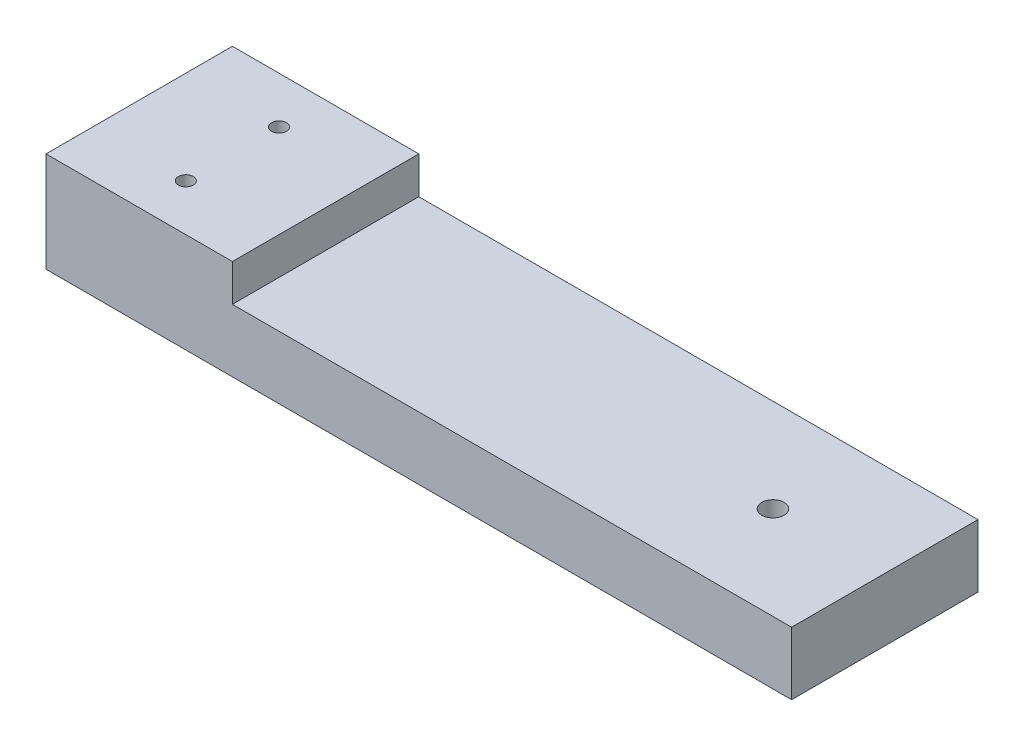
SolidWorks part; units mm, degrees
material "Balsa"
ref_plane "Front Plane" through (0, 0, 0) normal (0, 0, 1) x (1, 0, 0)
ref_plane "Top Plane" through (0, 0, 0) normal (0, 1, 0) x (1, 0, 0)
ref_plane "Right Plane" through (0, 0, 0) normal (1, 0, 0) x (0, 0, -1)
sketch "Sketch1" plane through (0, 0, 0) normal (0, 1, 0) x (1, 0, 0)
  line L1 (0, 0) -> (50, 0)
  line L2 (0, 0) -> (0, 50)
  line L3 (0, 50) -> (50, 50)
  line L4 (50, 0) -> (50, 50)
  line L5 (0, 0) -> (50, 50) construction
  line L6 (0, 50) -> (50, 0) construction
  line L7 (0, 50) -> (200, 50)
  line L8 (0, 50) -> (0, 0)
  line L9 (0, 0) -> (200, 0)
  line L10 (200, 50) -> (200, 0)
  line L11 (0, 50) -> (200, 0) construction
  line L12 (0, 0) -> (200, 50) construction
  point P4 (25, 25)
  point P8 (100, 25)
  dimension "D1" = 50
  dimension "D3" = 150
  dimension "D4" = 50
extrude "Boss-Extrude1" add sketch "Sketch1" along normal blind 26.8 contours L1 L4 L3 L2 region at (25, 0, -25)
extrude "Boss-Extrude2" add sketch "Sketch1<3>" along normal blind 16.85 contours L10 L7 L4 L9 region at (125, 0, -25)
sketch "Sketch1<3>" plane through (0, 0, 0) normal (0, 1, 0) x (1, 0, 0) same geometry as "Sketch1"
sketch "Sketch2" plane through (0, 0, 0) normal (0, -1, 0) x (1, 0, 0)
  line L0 (0, 0) -> (50, 0) construction
  line L1 (0, 0) -> (200, 0) construction
  line L2 (25, 0) -> (25, -50)
  line L3 (0, -50) -> (200, -50) construction
  line L4 (25, -25) -> (150, -25)
  line L5 (200, -50) -> (200, 0) construction
  circle A0 centre (25, -37.5) radius 2
  circle A1 centre (25, -12.5) radius 2
  circle A2 centre (170, -25) radius 3
  point P5 (25, 0)
  dimension "D2" = 25
  dimension "D3" = 12.5
  dimension "D4" = 4
  dimension "D5" = 4
  dimension "D6" = 6
  dimension "D7" = 30
  dimension "D1" = 50
  dimension "D8" = 25
extrude "Cut-Extrude1" cut sketch "Sketch2" against normal through all contours A1 | A0 | A2
